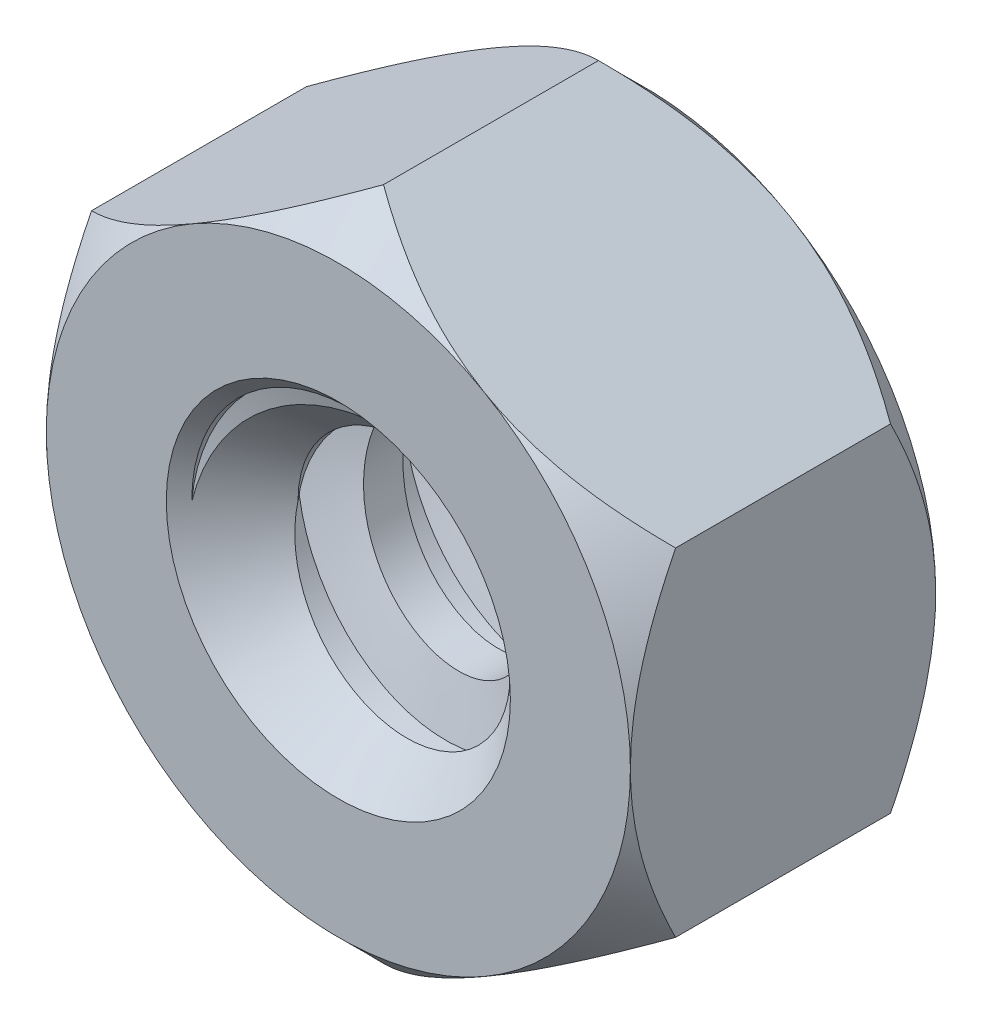
SolidWorks part; units mm, degrees
ref_plane "Front" through (0, 0, 0) normal (0, 0, 1) x (1, 0, 0)
ref_plane "Top" through (0, 0, 0) normal (0, 1, 0) x (1, 0, 0)
ref_plane "Right" through (0, 0, 0) normal (1, 0, 0) x (0, 0, -1)
sketch "Sketch1" plane through (0, 0, 0) normal (0, 0, 1) x (1, 0, 0)
  line L1 (0, -10.082) -> (8.7312, -5.041)
  line L2 (8.7312, -5.041) -> (8.7312, 5.041)
  line L3 (8.7312, 5.041) -> (0, 10.082)
  line L4 (0, 10.082) -> (-8.7312, 5.041)
  line L5 (-8.7312, 5.041) -> (-8.7312, -5.041)
  line L6 (-8.7312, -5.041) -> (0, -10.082)
  circle A0 centre (0, 0) radius 8.7312 construction
  circle A1 centre (0, 0) radius 4.7625
  dimension "Width" = 17.4625
  dimension "ThreadDia" = 9.525
extrude "Boss-Extrude1" add sketch "Sketch1" along normal mid plane 9.1281
sketch "Sketch2" plane through (0, 0, 4.5641) normal (0, 0, 1) x (1, 0, 0)
  circle A0 centre (0, 0) radius 4.7625 construction
  circle A1 centre (0, 0) radius 4.7625
curve "Helix/Spiral1" pitch 3.175 height 12.3031 radius 4.7625 centre (0, 0, 4.5641) axis (0, 0, -1) start towards (0, 1, 0) parameters "Pitch"=3.175
sketch "Sketch3" plane through (0, 0, 0) normal (1, 0, 0) x (0, 0, -1)
  line L0 (-4.5641, 4.7625) -> (-4.9746, 3.1751)
  line L1 (-4.5641, 5.041) -> (-4.5641, -5.041) construction
  line L2 (-4.5641, 4.7625) -> (-4.5641, -4.7625) construction
  line L3 (-4.9746, 3.1751) -> (-6.1516, 3.1751)
  line L4 (-6.1516, 3.1751) -> (-6.5621, 4.7625)
  line L5 (-6.5621, 4.7625) -> (-4.5641, 4.7625)
  line L6 (-6.3568, 3.9688) -> (-4.7693, 3.9688) construction
  line L7 (-5.5631, 3.9688) -> (-5.5631, 3.1751) construction
  spline S0 degree 3 poles (-4.5641, 4.7625) (-4.4983, 4.7625) (-4.3654, 4.5145) (-4.1672, 3.4553) (-3.9687, 1.87) (-3.7703, 0) (-3.5719, -1.87) (-3.3734, -3.4553) (-3.175, -4.5145) (-2.9766, -4.8865) (-2.7781, -4.5145) (-2.5797, -3.4553) (-2.3812, -1.87) (-2.1828, 0) (-1.9844, 1.87) (-1.7859, 3.4553) (-1.5875, 4.5145) (-1.3891, 4.8865) (-1.1906, 4.5145) (-0.9922, 3.4553) (-0.7937, 1.87) (-0.5953, 0) (-0.3969, -1.87) (-0.1984, -3.4553) (0, -4.5145) (0.1984, -4.8865) (0.3969, -4.5145) (0.5953, -3.4553) (0.7937, -1.87) (0.9922, 0) (1.1906, 1.87) (1.3891, 3.4553) (1.5875, 4.5145) (1.7859, 4.8865) (1.9844, 4.5145) (2.1828, 3.4553) (2.3812, 1.87) (2.5797, 0) (2.7781, -1.87) (2.9766, -3.4553) (3.175, -4.5145) (3.3734, -4.8865) (3.5719, -4.5145) (3.7703, -3.4553) (3.9687, -1.87) (4.1672, 0) (4.3656, 1.87) (4.5641, 3.4553) (4.7625, 4.5145) (4.9609, 4.8865) (5.1594, 4.5145) (5.3578, 3.4553) (5.5562, 1.87) (5.7547, 0) (5.9531, -1.87) (6.1516, -3.4553) (6.35, -4.5145) (6.5484, -4.8865) (6.7469, -4.5145) (6.9453, -3.4552) (7.1437, -1.8701) (7.3422, 0.0003) (7.5404, 1.8687) (7.6733, 2.9296) (7.7391, 3.3676) knots 0 0 0 0 0.016129 0.032258 0.048387 0.064516 0.080645 0.096774 0.112903 0.129032 0.145161 0.16129 0.177419 0.193548 0.209677 0.225806 0.241935 0.258065 0.274194 0.290323 0.306452 0.322581 0.33871 0.354839 0.370968 0.387097 0.403226 0.419355 0.435484 0.451613 0.467742 0.483871 0.5 0.516129 0.532258 0.548387 0.564516 0.580645 0.596774 0.612903 0.629032 0.645161 0.66129 0.677419 0.693548 0.709677 0.725806 0.741935 0.758065 0.774194 0.790323 0.806452 0.822581 0.83871 0.854839 0.870968 0.887097 0.903226 0.919355 0.935484 0.951613 0.967742 0.983871 1 1 1 1 construction
  dimension "D1" = 29
  dimension "D2" = 1.177
  dimension "D3" = 1.5875
sketch "Sketch4" plane through (0, 0, 4.5641) normal (0, 0, 1) x (1, 0, 0)
  circle A0 centre (0, 0) radius 5.1435
  circle A1 centre (0, 0) radius 4.7625 construction
  dimension "D1" = 0.381
sketch "Sketch5" plane through (0, 0, -4.5641) normal (0, 0, -1) x (-1, 0, 0)
  circle A1 centre (0, 0) radius 5.1435
  circle A2 centre (0, 0) radius 5.1435
  dimension "D1" = 0
sweep "Sweep1" add profiles "Sketch3" path "Helix/Spiral1"
extrude "Cut-Extrude1" cut sketch "Sketch4" along normal through all
extrude "Cut-Extrude2" cut sketch "Sketch5" along normal through all
extrude "Cut-Extrude3" cut sketch "Sketch4<2>" against normal through all draft 45
sketch "Sketch4<2>" plane through (0, 0, 4.5641) normal (0, 0, 1) x (1, 0, 0) same geometry as "Sketch4"
extrude "Cut-Extrude4" cut sketch "Sketch5<2>" against normal through all draft 45
sketch "Sketch5<2>" plane through (0, 0, -4.5641) normal (0, 0, -1) x (-1, 0, 0) same geometry as "Sketch5"
sketch "Sketch6" plane through (0, 0, 4.5641) normal (0, 0, 1) x (1, 0, 0)
  line L0 (-8.7313, 0) -> (0, 0) construction
  line L2 (-8.7312, 5.041) -> (-8.7312, -5.041) construction
  circle A0 centre (0, 0) radius 8.7313
extrude "Cut-Extrude5" cut sketch "Sketch6" against normal through all draft 45 flip side to cut
sketch "Sketch7" plane through (0, 0, -4.5641) normal (0, 0, -1) x (-1, 0, 0)
  circle A1 centre (0, 0) radius 8.7313
  circle A2 centre (0, 0) radius 8.7313
  dimension "D1" = 0
extrude "Cut-Extrude6" cut sketch "Sketch7" against normal through all draft 45 flip side to cut
ref_point "Point1"
ref_point "Point2"
ref_axis "Axis1" through (0, 0, -4.5641) along (0, 0, 1)
equation "\"D3@Helix/Spiral1\" = \"Height@Boss-Extrude1\"+\"Pitch@Helix/Spiral1\""
equation "\"D2@Sketch3\" = \"Pitch@Helix/Spiral1\"*.3707"
equation "\"D3@Sketch3\" = \"Pitch@Helix/Spiral1\"*.5"
